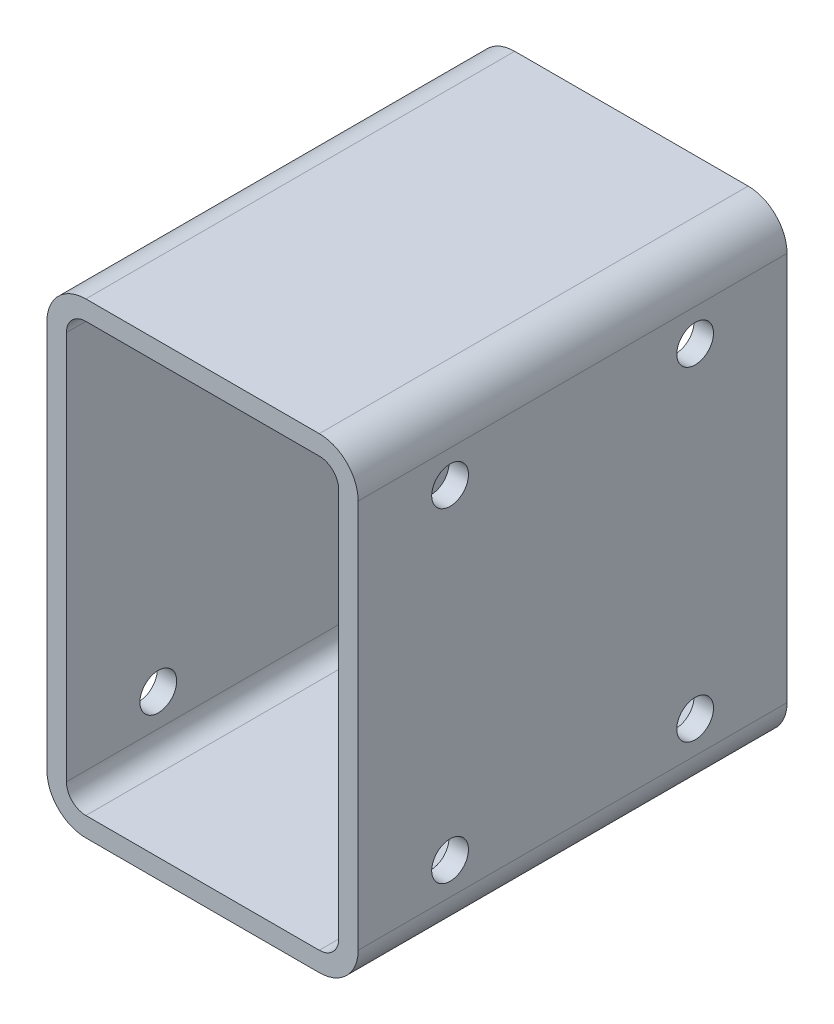
SolidWorks part; units mm, degrees
material "Plain Carbon Steel"
ref_plane "Front Plane" through (0, 0, 0) normal (0, 0, 1) x (1, 0, 0)
ref_plane "Top Plane" through (0, 0, 0) normal (0, 1, 0) x (1, 0, 0)
ref_plane "Right Plane" through (0, 0, 0) normal (1, 0, 0) x (0, 0, -1)
sketch "Sketch3" plane through (0, 0, 0) normal (1, 0, 0) x (0, 0, -1)
  line L0 (-35, 0) -> (35, 0)
  dimension "D1" = 70
other "Cnc 3X2X0.125(1)" corner treatment miter
ref_plane "Plane1" through (0, 0, 35) normal (0, 0, -1) x (0, 1, 0)
sketch "Sketch12" plane through (0, 0, 35) normal (0, 0, -1) x (0, 1, 0)
  line L0 (31.75, 22.225) -> (-31.75, 22.225)
  line L1 (31.75, -25.4) -> (-31.75, -25.4)
  line L2 (38.1, -19.05) -> (38.1, 19.05)
  line L3 (31.75, 25.4) -> (-31.75, 25.4)
  line L4 (-38.1, -19.05) -> (-38.1, 19.05)
  line L5 (38.1, -25.4) -> (-38.1, 25.4) construction
  line L6 (38.1, 25.4) -> (-38.1, -25.4) construction
  line L7 (-34.925, -19.05) -> (-34.925, 19.05)
  line L8 (31.75, -22.225) -> (-31.75, -22.225)
  line L9 (34.925, -19.05) -> (34.925, 19.05)
  line L10 (38.1, -25.4) -> (-38.1, -25.4) construction
  line L11 (-38.1, -25.4) -> (-38.1, 25.4) construction
  line L12 (38.1, -25.4) -> (38.1, 25.4) construction
  line L13 (38.1, 25.4) -> (-38.1, 25.4) construction
  line L14 (-34.925, -22.225) -> (-34.925, 22.225) construction
  line L15 (34.925, -22.225) -> (-34.925, -22.225) construction
  line L16 (34.925, -22.225) -> (34.925, 22.225) construction
  line L17 (34.925, 22.225) -> (-34.925, 22.225) construction
  arc A0 (-31.75, -25.4) -> (-38.1, -19.05) centre (-31.75, -19.05) cw
  arc A1 (31.75, -25.4) -> (38.1, -19.05) centre (31.75, -19.05) ccw
  arc A2 (38.1, 19.05) -> (31.75, 25.4) centre (31.75, 19.05) ccw
  arc A3 (-31.75, 25.4) -> (-38.1, 19.05) centre (-31.75, 19.05) ccw
  arc A4 (-34.925, -19.05) -> (-31.75, -22.225) centre (-31.75, -19.05) ccw
  arc A5 (31.75, -22.225) -> (34.925, -19.05) centre (31.75, -19.05) ccw
  arc A6 (31.75, 22.225) -> (34.925, 19.05) centre (31.75, 19.05) cw
  arc A7 (-31.75, 22.225) -> (-34.925, 19.05) centre (-31.75, 19.05) ccw
  point P0 (0, 0)
  point P34 (0, 0)
  dimension "D4" = 6.35
  dimension "D5" = 3.175
  dimension "D1" = 76.2
  dimension "D2" = 50.8
  dimension "D3" = 3.175
sketch "Sketch2" plane through (0, 0, 0) normal (1, 0, 0) x (0, 0, -1)
  line L1 (20, -26.5) -> (-20, -26.5) construction
  line L2 (20, -26.5) -> (20, 26.5) construction
  line L3 (20, 26.5) -> (-20, 26.5) construction
  line L4 (-20, -26.5) -> (-20, 26.5) construction
  line L5 (20, -26.5) -> (-20, 26.5) construction
  line L6 (20, 26.5) -> (-20, -26.5) construction
  circle A0 centre (-20, 26.5) radius 3
  circle A1 centre (20, 26.5) radius 3
  circle A2 centre (20, -26.5) radius 3
  circle A3 centre (-20, -26.5) radius 3
  point P0 (0, 0)
  dimension "D3" = 6
  dimension "D1" = 40
  dimension "D2" = 53
extrude "Cut-Extrude1" cut sketch "Sketch2" against normal through all both and the other way through all
equation "\"M5_tap\"=4.2mm\t\t\t\t\t\t\t' Below you can do mesurements as follows: cm, mm, ft, in, m, "
equation "\"M5_clearence\"=5.5mm"
equation "\"M6_tap\"=5mm"
equation "\"M6_clearence\"=6.6mm"
equation "\"work_area_width\"=1100mm"
equation "\"work_area_depth\"=900mm"
equation "\"D1\"= \"work_area_depth\" + 200"
equation "\"steel_base_width\"=3in\t"
equation "\"steel_base_height\"=2in"
equation "\"steel_base_wall_thickness\"=0.125in"
equation "\"steel_base_radius\"=6mm"
equation "\"steel_sides_width\"=3in\t\t\t\t\t'this tube is rotated so flip width/height"
equation "\"steel_sides_height\"=2in\t\t\t\t'this tube is rotated so flip width/height"
equation "\"steel_sides_wall_thickness\"=0.125in"
equation "\"steel_sides_radius\"=6mm"
equation "\"steel_gantry_width\"=4in\t\t\t\t'this tube is rotated so flip width/height"
equation "\"steel_gantry_height\"=3in\t\t\t\t'this tube is rotated so flip width/height"
equation "\"steel_gantry_wall_thickness\"=0.125in"
equation "\"steel_gantry_radius\"=6mm"
equation "\"steel_rollers_width\"=3in"
equation "\"steel_rollers_height\"=2in\t\t\t\t'keep as low as possible as this increases how big plastic parts are"
equation "\"steel_rollers_wall_thickness\"=0.125in"
equation "\"steel_rollers_radius\"=6mm"
equation "\"steel_zbox_width\"=4in\t\t\t\t\t'if the gantry height (rotated) is too thick, a wider zbox is necessary"
equation "\"steel_zbox_height\"=2in\t\t\t\t\t'hole patteren changes as the zbox and gantry height (rotated) changes."
equation "\"steel_zbox_wall_thickness\"=0.125in"
equation "\"steel_zbox_radius\"=6mm"
